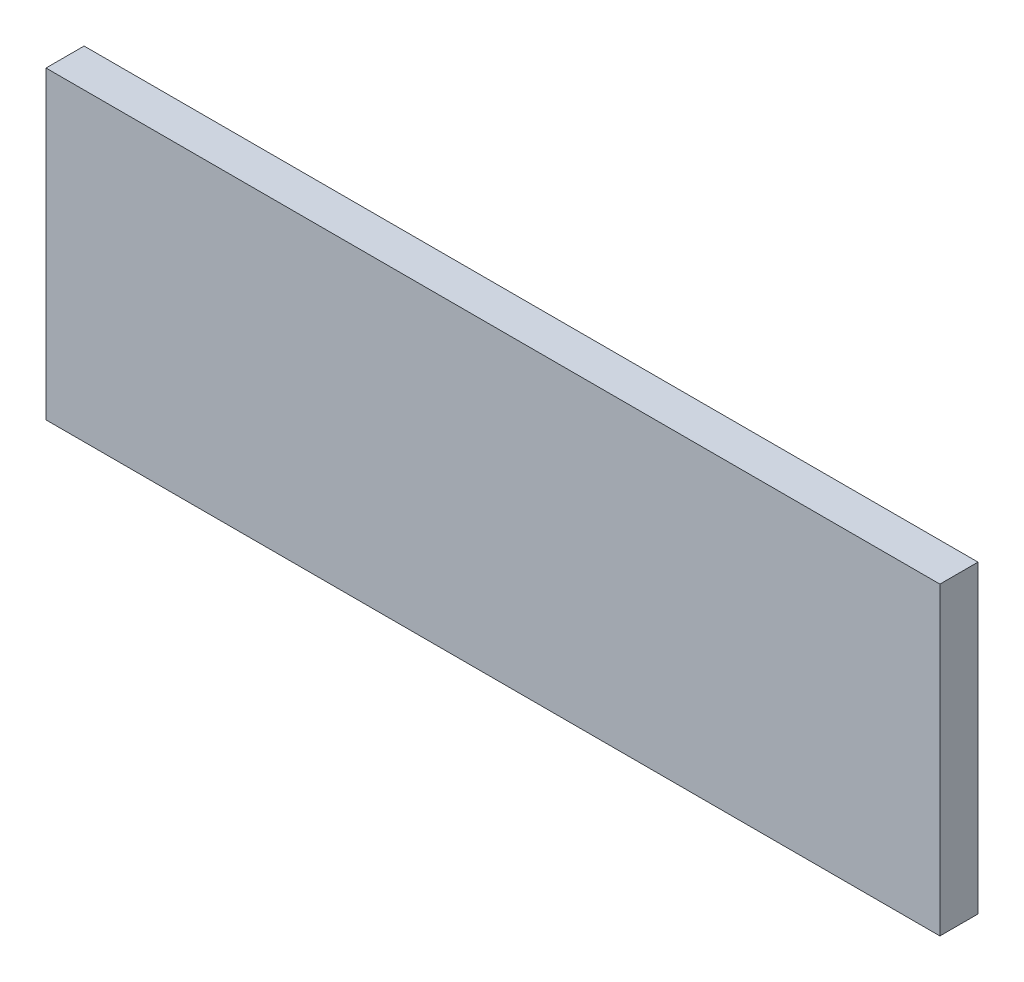
SolidWorks part; units mm, degrees
material "Pine"
ref_plane "Front Plane" through (0, 0, 0) normal (0, 0, 1) x (1, 0, 0)
ref_plane "Top Plane" through (0, 0, 0) normal (0, 1, 0) x (1, 0, 0)
ref_plane "Right Plane" through (0, 0, 0) normal (1, 0, 0) x (0, 0, -1)
sketch "Sketch1" plane through (0, 0, 0) normal (0, 0, 1) x (1, 0, 0)
  line L1 (-103.855, 49.3214) -> (175.545, 49.3214)
  line L2 (-103.855, 49.3214) -> (-103.855, -45.9286)
  line L3 (-103.855, -45.9286) -> (175.545, -45.9286)
  line L4 (175.545, 49.3214) -> (175.545, -45.9286)
  dimension "D1" = 279.4
  dimension "D2" = 95.25
extrude "Boss-Extrude1" add sketch "Sketch1" along normal blind 11.9062
